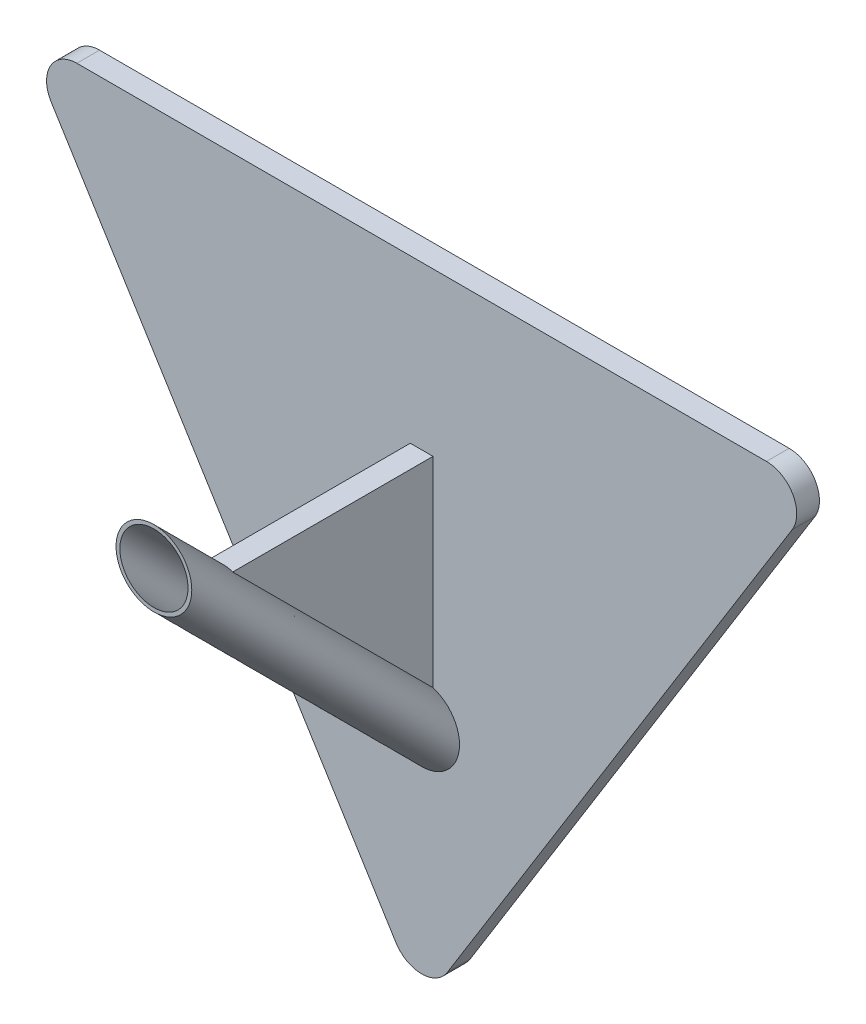
SolidWorks part; units mm, degrees
ref_plane "Plan de face" through (0, 0, 0) normal (0, 0, 1) x (1, 0, 0)
ref_plane "Plan de dessus" through (0, 0, 0) normal (0, 1, 0) x (1, 0, 0)
ref_plane "Plan de droite" through (0, 0, 0) normal (1, 0, 0) x (0, 0, -1)
sketch "Esquisse1" plane through (0, 0, 0) normal (0, 0, 1) x (1, 0, 0)
  line L0 (0, 0) -> (-52.7264, 84.9701)
  line L1 (-52.7264, 84.9701) -> (52.7264, 84.9701)
  line L2 (52.7264, 84.9701) -> (0, 0)
  point P4 (0, 0)
  point P5 (0, 84.9701)
  dimension "D1" = 100
extrude "Boss.-Extru.1" add sketch "Esquisse1" along normal blind 3
sketch "Esquisse5" plane through (0, 0, 3) normal (0, 0, 1) x (1, 0, 0)
  circle A0 centre (0, 32.3029) radius 5
  dimension "D1" = 10
sketch "Esquisse6" plane through (0, 0, 0) normal (1, 0, 0) x (0, 0, -1)
  line L0 (-3, 32.3029) -> (-38.3553, 67.6582)
  line L1 (-3, 37.3029) -> (-3, 27.3029) construction
  line L2 (-3, 0) -> (-3, 84.9701) construction
  dimension "D1" = 45
  dimension "D2" = 50
sweep "Balayage1" add profiles "Esquisse5" path "Esquisse6"
sketch "Esquisse7" plane through (0, 0, 3) normal (0, 0, 1) x (1, 0, 0)
  circle A0 centre (0, 32.3029) radius 4.5
  dimension "D1" = 9
sweep "Enlèvement de matière-Balayage1" cut profiles "Esquisse7" path "Esquisse6<2>"
sketch "Esquisse6<2>" plane through (0, 0, 0) normal (1, 0, 0) x (0, 0, -1) same geometry as "Esquisse6"
sketch "Esquisse10" plane through (0, 0, 0) normal (1, 0, 0) x (0, 0, -1)
  line L0 (-29.2261, 63.529) -> (-3, 63.529)
  line L1 (-3, 37.3029) -> (-38.3553, 72.6582) construction
  line L2 (-3, 0) -> (-3, 84.9701) construction
rib "Nervure4" sketch "Esquisse10" sketch "Esquisse10" thickness 3 extrusion direction parallel to sketch draft on no parameters "D1"=3
fillet "Congé1" radius 4 3 edges at (0, 0, 1.5) (-52.7264, 84.9701, 1.5) (52.7264, 84.9701, 1.5)
